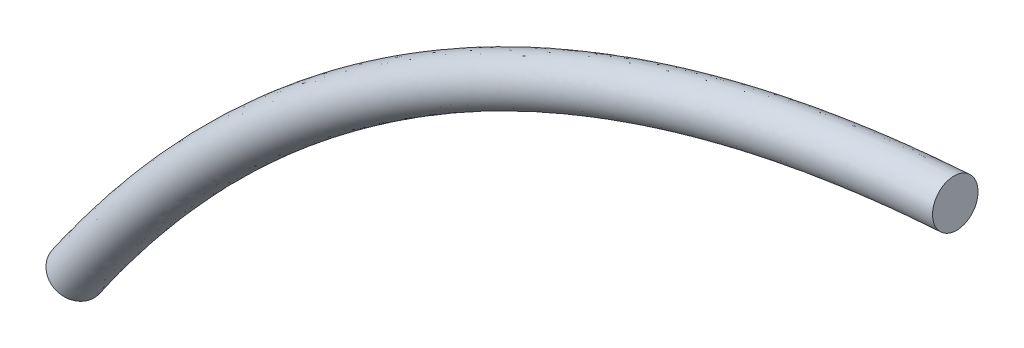
SolidWorks part; units mm, degrees
material "Custom Plastic"
ref_plane "X-Y Datum" through (0, 0, 0) normal (0, 0, 1) x (1, 0, 0)
ref_plane "X-Z Datum" through (0, 0, 0) normal (0, 1, 0) x (1, 0, 0)
ref_plane "Y-Z Datum" through (0, 0, 0) normal (1, 0, 0) x (0, 0, -1)
sketch3d "3DSketch1"
  circle A0 centre (-244.2256, -166.5107, 163.3218) radius 2.9 construction
  circle A1 centre (-71.1484, -53.4906, 175.7553) radius 2.5781 construction
  circle A3 centre (-244.2256, -166.5107, 163.3218) radius 3.475 construction
  spline S0 degree 2 poles (-244.2256, -166.5107, 163.3218) (-165.5256, -58.6994, 176.3729) (-50.6871, -51.34, 175.7553) knots 0 0 0 1 1 1
  point P0 (-244.2256, -166.5107, 163.3218)
  point P1 (-71.1484, -53.4906, 175.7553)
  point P4 (-246.0339, -168.7779, 163.3218)
  point P8 (-73.7124, -53.7601, 175.7553)
  point P16 (-246.3925, -169.2274, 163.3218)
sweep "Sweep1" add path "3DSketch1" circular profile diameter 9.398 parameters "D3"=9.398
